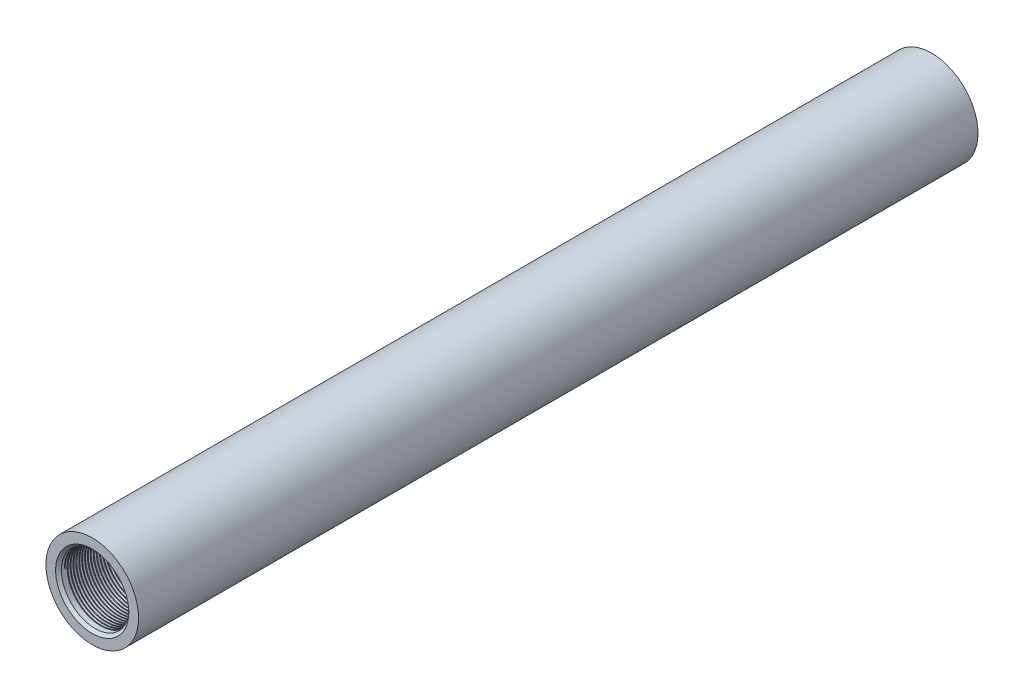
SolidWorks part; units mm, degrees
ref_plane "Ön Düzlem" through (0, 0, 0) normal (0, 0, 1) x (1, 0, 0)
ref_plane "Üst Düzlem" through (0, 0, 0) normal (0, 1, 0) x (1, 0, 0)
ref_plane "Sağ Düzlem" through (0, 0, 0) normal (1, 0, 0) x (0, 0, -1)
sketch "Çizim1" plane through (0, 0, 0) normal (0, 0, 1) x (1, 0, 0)
  circle A0 centre (0, 0) radius 16
  circle A1 centre (0, 0) radius 11.65
  dimension "D1" = 32
  dimension "D2" = 4.35
extrude "Yükseklik-Ekstrüzyon1" add sketch "Çizim1" along normal blind 290
chamfer "Pah1" distance 1 angle 45 1 edges at (11.65, 0, 290)
thread "Diş1" pitch 0.3175 method extrude profile "Diş Profili2" start angle 0, offset 1, length 20, pitch 1, diameter 23.3
ref_plane "Düzlem2" through (-11.65, 0, 288) normal (0, -1, 0) x (-1, 0, 0)
sketch "Diş Profili2" plane through (-11.65, 0, 288) normal (0, -1, 0) x (-1, 0, 0)
  line L0 (0, 0) -> (0, 0.3175) construction
  line L11 (0, 0) -> (0, 0.2778)
  line L12 (0, 0.2778) -> (-0.1719, 0.1786)
  line L13 (-0.1719, 0.1786) -> (-0.1719, 0.0992)
  line L15 (-0.1719, 0.0992) -> (0, 0)
  line L17 (-0.1719, 0.1389) -> (0, 0.1389) construction
  point P2 (0, 0)
  dimension "Pitch" = 0.3175
  dimension "Profile_Angle" = 60
  dimension "Profile_Land" = 0.0794
  dimension "Profile_Height" = 0.1719
chamfer "Pah2" distance 1 angle 45 1 edges at (11.65, 0, 0)
thread "Diş2" pitch 0.3175 method extrude profile "Diş Profili3" start angle 0, offset 0, length 20, pitch 1, diameter 23.3
ref_plane "Düzlem3" through (11.65, 0, 1) normal (0, -1, 0) x (1, 0, 0)
sketch "Diş Profili3" plane through (11.65, 0, 1) normal (0, -1, 0) x (1, 0, 0)
  line L0 (0, 0) -> (0, 0.3175) construction
  line L11 (0, 0) -> (0, 0.2778)
  line L12 (0, 0.2778) -> (-0.1719, 0.1786)
  line L13 (-0.1719, 0.1786) -> (-0.1719, 0.0992)
  line L15 (-0.1719, 0.0992) -> (0, 0)
  line L17 (-0.1719, 0.1389) -> (0, 0.1389) construction
  point P2 (0, 0)
  dimension "Pitch" = 0.3175
  dimension "Profile_Angle" = 60
  dimension "Profile_Land" = 0.0794
  dimension "Profile_Height" = 0.1719
